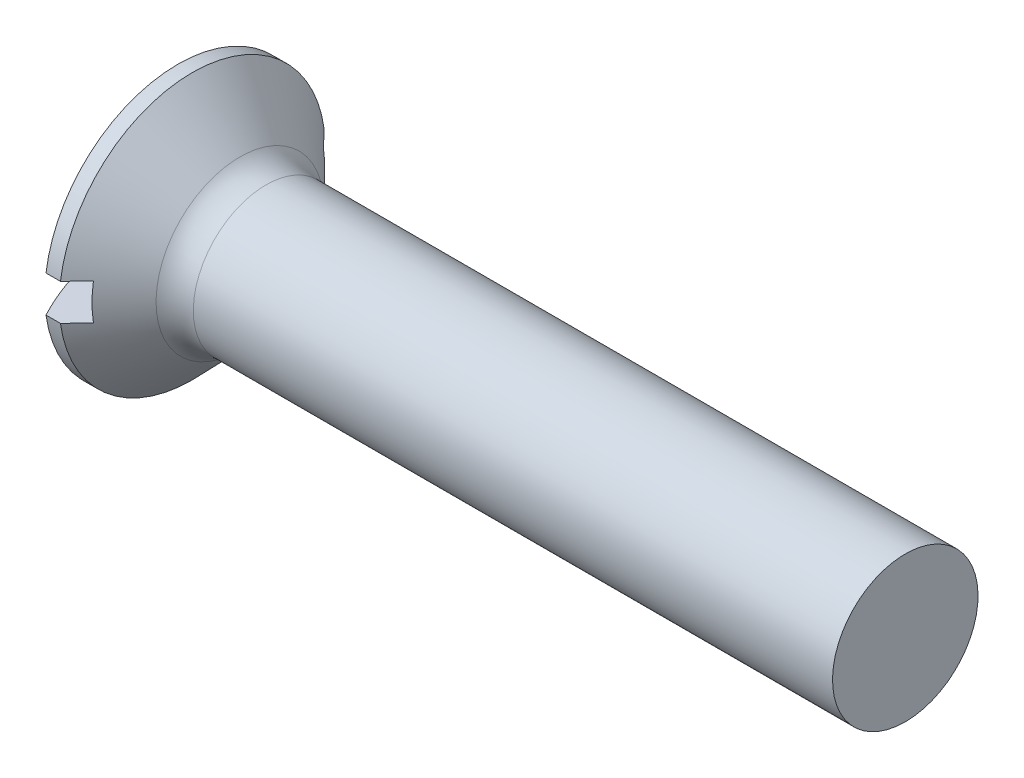
SolidWorks part; units mm, degrees
ref_plane "Front Plane" through (0, 0, 0) normal (0, 0, 1) x (1, 0, 0)
ref_plane "Top Plane" through (0, 0, 0) normal (0, 1, 0) x (1, 0, 0)
ref_plane "Right Plane" through (0, 0, 0) normal (1, 0, 0) x (0, 0, -1)
sketch "BodySke" plane through (0, 0, 0) normal (0, 0, 1) x (1, 0, 0)
  line L0 (2.3, 0) -> (111.3824, 0) construction
  line L1 (2.3, 0) -> (2.3, 9.15) construction
  line L2 (2.3, 9.15) -> (3.2924, 9.15)
  line L3 (3.2924, 9.15) -> (7.3, 5)
  line L4 (7.3, 5) -> (52.3, 5)
  line L5 (52.3, 5) -> (52.3, 0)
  line L6 (8.8, 8.824) -> (8.8, -5.8939) construction
  line L7 (2.3, 0) -> (52.3, 0)
  line L8 (14.3, 8.824) -> (14.3, -4.958) construction
  line L9 (2.3, -9.15) -> (3.2924, -9.15) construction
  line L10 (3.2924, -9.15) -> (7.3, -5) construction
  line L11 (7.3, -5) -> (52.3, -5) construction
  line L12 (2.3, 0) -> (-13.4753, 0) construction
  line L13 (0, 0) -> (0, 11.6167) construction
  line L14 (2.3, 0) -> (0, 0)
  arc A0 (0, 0) -> (2.3, 9.15) centre (19.3505, 0) cw
  point P10 (52.3, 4.172)
  dimension "Thread_minor" = 8.344
  dimension "Length" = 50
  dimension "Head_dia" = 18.3
  dimension "Advance" = 1.5
  dimension "Thread_length" = 38
revolve "BaseBody" add sketch "BodySke" angle 360 about L0
cosmetic thread "ThreadCosmetic" [suppressed] parameters "Thread_length"=38, "Thread_minor"=8.344
fillet "Fillet1" radius 2.5 1 edges at (7.3, -5, 0)
sketch "SlotSke" plane through (0, 0, 0) normal (1, 0, 0) x (0, 0, -1)
  line L1 (-9.15, 1.25) -> (9.15, 1.25)
  line L2 (-9.15, 1.25) -> (-9.15, -1.25)
  line L3 (-9.15, -1.25) -> (9.15, -1.25)
  line L4 (9.15, 1.25) -> (9.15, -1.25)
  dimension "D1" = 18.3
  dimension "D2" = 9.15
  dimension "D3" = 1.25
extrude "Slot" cut sketch "SlotSke" along normal blind 4.4
sketch "ThdSchSke" plane through (0, 0, 0) normal (0, 0, 1) x (1, 0, 0)
  line L0 (0, 0) -> (55.1256, 0) construction
  line L1 (2.3, 0) -> (111.3824, 0) construction
  line L2 (51.822, 5) -> (51.822, 5.9561)
  line L3 (51.822, 5.9561) -> (52.778, 5.9561)
  line L4 (52.778, 5.9561) -> (52.778, 5)
  line L5 (52.778, 5) -> (52.3, 4.172)
  line L6 (52.3, 4.172) -> (51.822, 5)
  line L7 (7.3, 5) -> (52.3, 5) construction
  line L13 (52.3, 5) -> (52.3, 0) construction
revolve "ThreadSchematic" [suppressed] cut sketch "ThdSchSke" angle 360 about L0
pattern_linear "ThdSchPat" [suppressed] count 26 along (-1, 0, 0) of bodies 103
equation "\"Thread_minor@ThreadCosmetic\" = \"Thread_minor@BodySke\""
equation "\"Thread_length@ThreadCosmetic\" = \"Thread_length@BodySke\""
equation "\"D1@SlotSke\" = \"Head_dia@BodySke\""
equation "\"D2@SlotSke\" = \"D1@SlotSke\" / 2"
equation "\"D3@SlotSke\" = \"Slot_width@SlotSke\" / 2"
equation "\"Advance@ThdSchPat\" = \"Advance@BodySke\""
equation "\"D1@ThdSchPat\" =  int( \"Thread_length@BodySke\" / \"Advance@ThdSchPat\" )  + 1"
